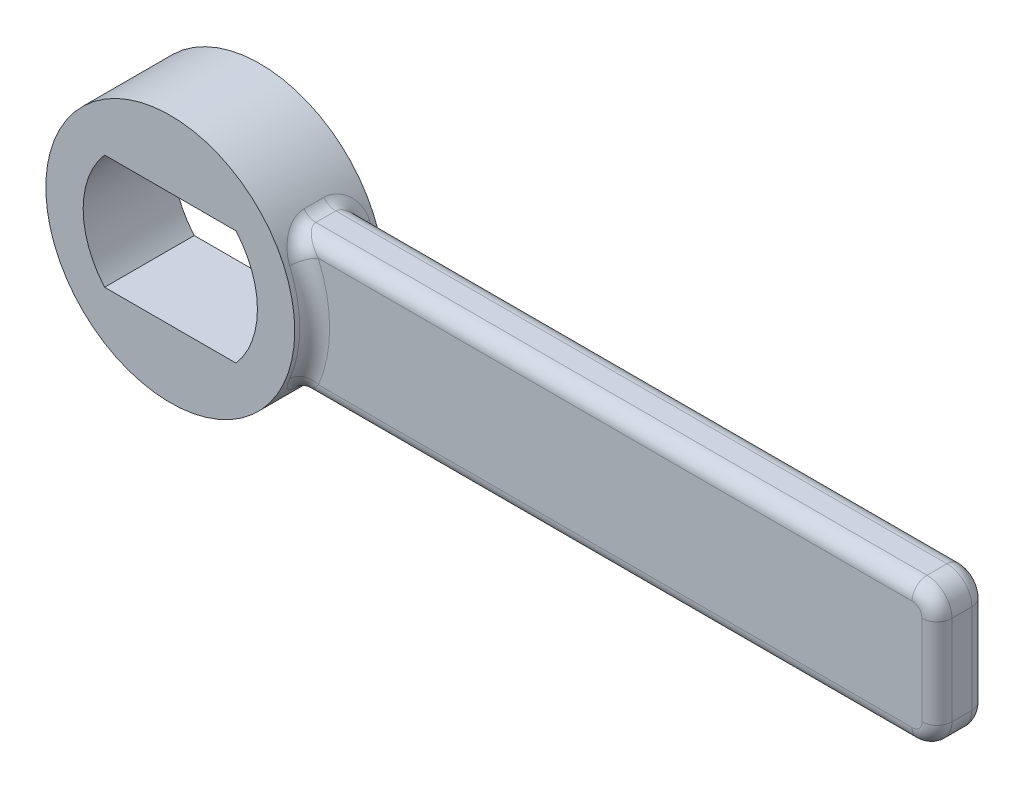
SolidWorks part; units mm, degrees
material "Сталь"
ref_plane "Спереди" through (0, 0, 0) normal (0, 0, 1) x (1, 0, 0)
ref_plane "Сверху" through (0, 0, 0) normal (0, 1, 0) x (1, 0, 0)
ref_plane "Справа" through (0, 0, 0) normal (1, 0, 0) x (0, 0, -1)
sketch "Эскиз1" plane through (0, 0, 0) normal (0, 0, 1) x (1, 0, 0)
  line L0 (0, 0) -> (25, 0) construction
  line L1 (150, -14) -> (0, -14)
  line L2 (150, -14) -> (150, 14)
  line L3 (150, 14) -> (0, 14)
  line L4 (0, -14) -> (0, 14)
  line L5 (150, -14) -> (0, 14) construction
  line L6 (150, 14) -> (0, -14) construction
  line L8 (-13.1909, 11.5) -> (13.1909, 11.5)
  line L9 (-13.1909, -11.5) -> (13.1909, -11.5)
  circle A0 centre (0, 0) radius 25
  circle A1 centre (0, 0) radius 17.5
  point P3 (75, 0)
  point P8 (0, 0)
  dimension "D1" = 50
  dimension "D4" = 35
  dimension "D2" = 28
  dimension "D3" = 150
  dimension "D5" = 23
extrude "Бобышка-Вытянуть1" add sketch "Эскиз1" along normal mid plane 18 contours A1 L3 A0 L1 | L3 A1 L8 L4 | L8 A1 L3 L4 | L9 A1 L1 L4 | L1 A1 L9 L4 | A1 L1 A0 L3 region at (-24.3225, 0, 0) region at (19.3618, 0, 0) region at (-2.2391, -14.4008, 0) region at (5.9952, -12.7033, 0) region at (5.9952, 12.7033, 0) region at (-2.2391, 14.4008, 0)
extrude "Бобышка-Вытянуть2" add sketch "Эскиз1<5>" along normal mid plane 10 contours A0 L1 L2 L3 region at (86.8056, 0, 0)
sketch "Эскиз1<5>" plane through (0, 0, 0) normal (0, 0, 1) x (1, 0, 0) same geometry as "Эскиз1"
fillet "Скругление3" radius 5 2 edges at (150, 14, 0) (150, -14, 0)
fillet "Скругление4" radius 3 14 edges at (20.7123, 14, 0) (25, 0, 5) (25, 0, -5) (82.8562, 14, -5) (148.5355, 12.5355, -5) (150, 0, -5) (148.5355, -12.5355, -5) (82.8562, 14, 5) (148.5355, 12.5355, 5) (150, 0, 5) (148.5355, -12.5355, 5) (20.7123, -14, 0) (82.8562, -14, -5) (82.8562, -14, 5)
